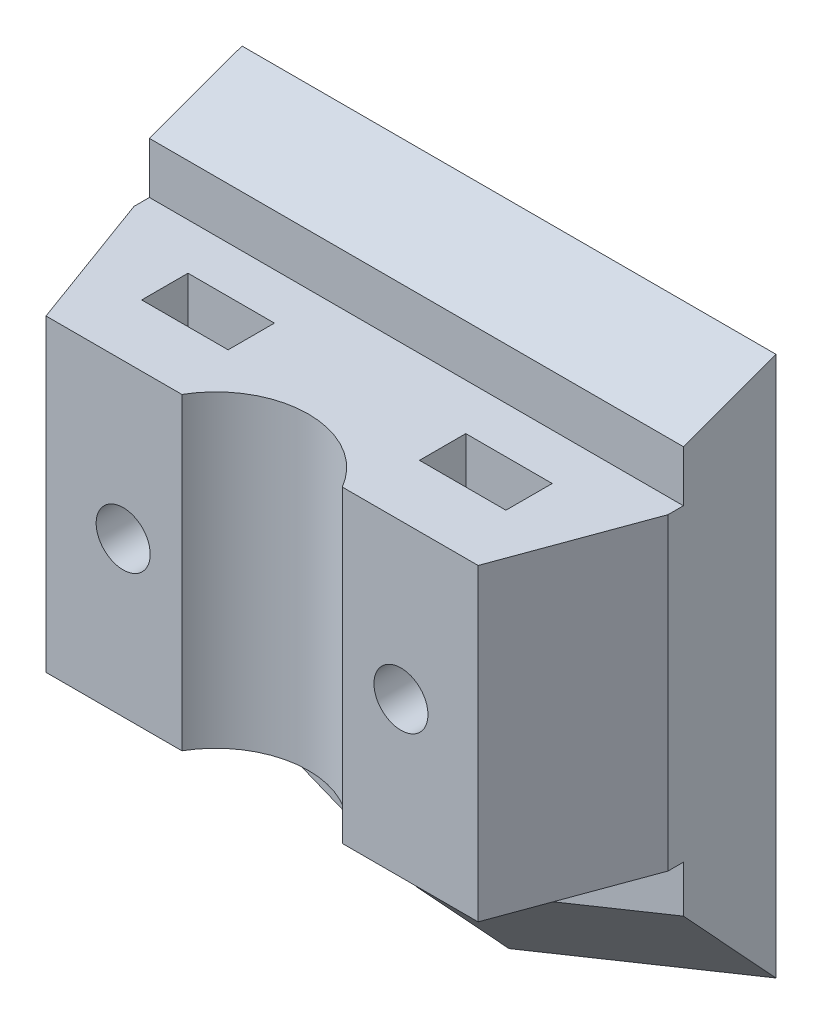
SolidWorks part; units mm, degrees
ref_plane "Plano frontal" through (0, 0, 0) normal (0, 0, 1) x (1, 0, 0)
ref_plane "Plano superior" through (0, 0, 0) normal (0, 1, 0) x (1, 0, 0)
ref_plane "Plano direito" through (0, 0, 0) normal (1, 0, 0) x (0, 0, -1)
sketch "Esboço1" plane through (0, 0, 0) normal (0, 0, 1) x (1, 0, 0)
  line L1 (-17.3, 13) -> (17.3, 13)
  line L2 (-17.3, 13) -> (-17.3, -13)
  line L3 (-17.3, -13) -> (17.3, -13)
  line L4 (17.3, 13) -> (17.3, -13)
  line L5 (-17.3, 13) -> (17.3, -13) construction
  line L6 (-17.3, -13) -> (17.3, 13) construction
  point P0 (0, 0)
  dimension "D1" = 34.6
  dimension "D2" = 26
extrude "Ressalto-extrusão1" add sketch "Esboço1" along normal blind 7
sketch "Esboço10" plane through (0, 0, 0) normal (0, 0, -1) x (-1, 0, 0)
  line L0 (-17.3, -19.5) -> (0, -26.5)
  line L1 (-17.3, 13) -> (17.3, 13)
  line L2 (-17.3, 13) -> (-17.3, 15.5)
  line L3 (-17.3, 15.5) -> (17.3, 15.5)
  line L4 (17.3, 13) -> (17.3, 15.5)
  line L5 (0, -26.5) -> (17.3, -19.5)
  line L6 (-17.3, -19.5) -> (-17.3, -13)
  line L7 (-17.3, -13) -> (17.3, -13)
  line L8 (17.3, -13) -> (17.3, -19.5)
  dimension "D1" = 7
  dimension "D2" = 35
  dimension "D3" = 2.5
extrude "Ressalto-extrusão4" add sketch "Esboço10" against normal up to surface (7 mm away) up to face at (0, 0, 7)
chamfer "Chanfro1" distance 7 angle 45 2 edges at (8.65, -23, 7) (-8.65, -23, 7)
chamfer "Chanfro2" distance 7 angle 20 1 edges at (0, 15.5, 7) first distance on face at (0, 15.5, 3.5)
sketch "Esboço11" plane through (0, 0, 0) normal (0, 1, 0) x (1, 0, 0)
  line L0 (-17.3, -7) -> (-14, -16)
  line L1 (17.3, -7) -> (-17.3, -7) construction
  line L2 (-14, -16) -> (-5.1962, -16)
  line L3 (-17.3, -7) -> (17.3, -7)
  line L4 (0, 0) -> (0, -18.2406) construction
  line L5 (-17.3, 0) -> (17.3, 0) construction
  line L6 (17.3, -7) -> (14, -16)
  line L7 (5.1962, -16) -> (14, -16)
  line L8 (11.8, -12) -> (6.2, -9) construction
  line L9 (-11.8, -9) -> (-6.2, -9)
  line L10 (-11.8, -9) -> (-11.8, -12)
  line L11 (-11.8, -12) -> (-6.2, -12)
  line L12 (-6.2, -9) -> (-6.2, -12)
  line L13 (-11.8, -9) -> (-6.2, -12) construction
  line L14 (-11.8, -12) -> (-6.2, -9) construction
  line L15 (11.8, -9) -> (6.2, -12) construction
  line L16 (6.2, -9) -> (6.2, -12)
  line L17 (11.8, -12) -> (6.2, -12)
  line L18 (11.8, -9) -> (11.8, -12)
  line L19 (11.8, -9) -> (6.2, -9)
  arc A0 (5.1962, -16) -> (-5.1962, -16) centre (0, -19) ccw
  point P12 (0, -7)
  point P13 (0, -16.2024)
  point P14 (-9, -10.5)
  point P21 (-10.9788, -16.2921)
  point P22 (-13.0665, -15)
  point P23 (-8.9608, -10.6207)
  point P24 (-15.7108, -7)
  point P25 (-17.3, -7)
  point P31 (9, -10.5)
  dimension "D2" = 6
  dimension "D3" = 3
  dimension "D1" = 9
  dimension "D4" = 5.6
  dimension "D5" = 3
  dimension "D6" = 18
  dimension "D7" = 2
  dimension "D8" = 28
extrude "Ressalto-extrusão5" add sketch "Esboço11" along normal mid plane 20
sketch "Esboço12" plane through (0, 0, 16) normal (0, 0, 1) x (1, 0, 0)
  line L0 (0, 0) -> (0, 7.5857) construction
  circle A0 centre (-9, 0) radius 1.75
  circle A1 centre (9, 0) radius 1.75
  point P5 (0, 0)
  dimension "D2" = 3.5
  dimension "D1" = 18
extrude "Corte-extrusão1" cut sketch "Esboço12" against normal blind 20
sketch "Esboço13" plane through (0, 0, 7) normal (0, 0, 1) x (1, 0, 0)
  line L0 (17.3, -11.9487) -> (17.3, -10) construction
  line L1 (-17.3, 10) -> (17.3, 10)
  line L2 (-17.3, 10) -> (-17.3, 15.5)
  line L3 (-17.3, 15.5) -> (17.3, 15.5)
  line L4 (17.3, 10) -> (17.3, 15.5)
  line L5 (-17.3, -10) -> (17.3, -10)
  line L6 (-17.3, -10) -> (-17.3, -28.3931)
  line L7 (-17.3, -28.3931) -> (17.3, -28.3931)
  line L8 (17.3, -10) -> (17.3, -28.3931)
  point P11 (17.3, -10)
extrude "Corte-extrusão2" cut sketch "Esboço13" against normal blind 1
